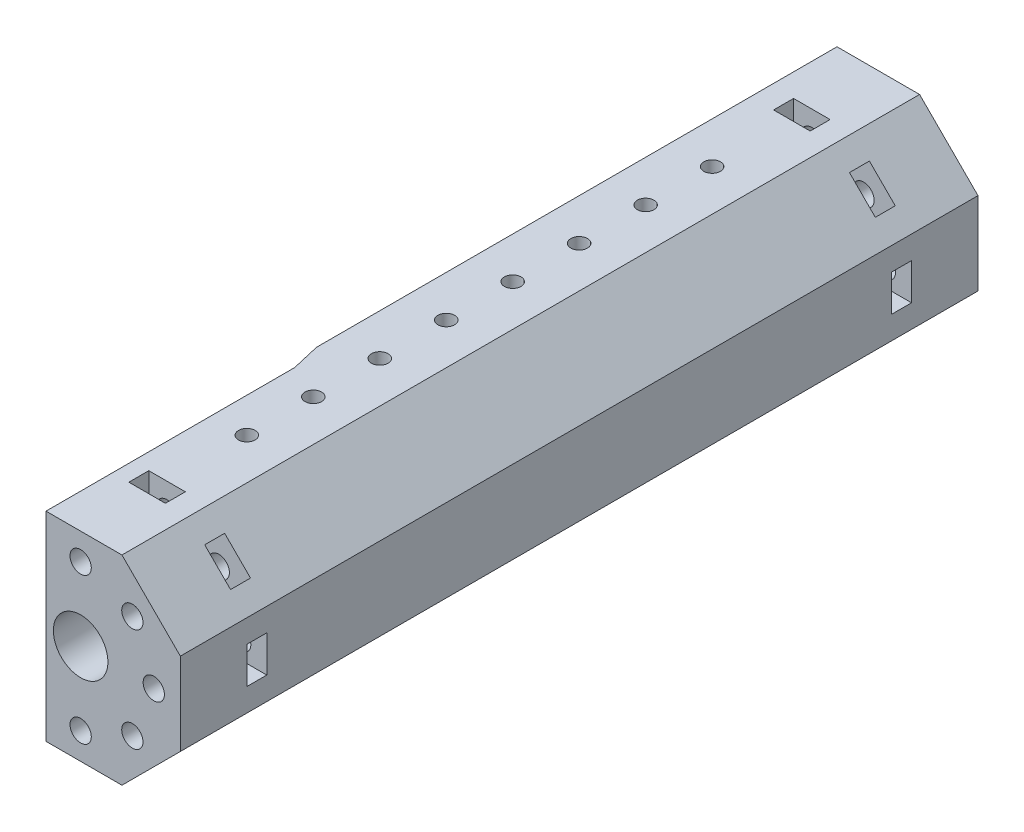
SolidWorks part; units mm, degrees
ref_plane "Alzado" through (0, 0, 0) normal (0, 0, 1) x (1, 0, 0)
ref_plane "Planta" through (0, 0, 0) normal (0, 1, 0) x (1, 0, 0)
ref_plane "Vista lateral" through (0, 0, 0) normal (1, 0, 0) x (0, 0, -1)
sketch "Croquis1" plane through (0, 0, 0) normal (0, 0, 1) x (1, 0, 0)
  line L1 (15, -6.2132) -> (15, 6.2132)
  line L2 (15, 6.2132) -> (6.2132, 15)
  line L3 (6.2132, 15) -> (-6.2132, 15)
  line L4 (-6.2132, 15) -> (-15, 6.2132)
  line L5 (-15, 6.2132) -> (-15, -6.2132)
  line L6 (-15, -6.2132) -> (-6.2132, -15)
  line L7 (-6.2132, -15) -> (6.2132, -15)
  line L8 (6.2132, -15) -> (15, -6.2132)
  circle A0 centre (0, 0) radius 15 construction
  dimension "D1" = 30
extrude "Saliente-Extruir1" add sketch "Croquis1" along normal blind 60
sketch "Croquis2" plane through (0, 0, 0) normal (0, 0, -1) x (-1, 0, 0)
  circle A0 centre (0, 11) radius 1.6
  circle A2 centre (7.7782, 7.7782) radius 1.6
  circle A3 centre (11, 0) radius 1.6
  circle A4 centre (7.7782, -7.7782) radius 1.6
  circle A5 centre (0, -11) radius 1.6
  circle A6 centre (-7.7782, -7.7782) radius 1.6
  circle A7 centre (-11, 0) radius 1.6
  circle A8 centre (-7.7782, 7.7782) radius 1.6
  point P22 (0, 0)
  dimension "D1" = 3.2
  dimension "D2" = 11
  dimension "D4" = 8
extrude "Cortar-Extruir1" cut sketch "Croquis2" against normal blind 20
sketch "Croquis3" plane through (0, 0, 0) normal (0, 0, -1) x (-1, 0, 0)
  line L0 (-2.75, 12.5877) -> (-2.75, 18.4632)
  line L1 (2.75, 12.5877) -> (0, 14.1754) construction
  line L2 (0, 14.1754) -> (-2.75, 12.5877) construction
  line L3 (-2.75, 12.5877) -> (-2.75, 9.4123)
  line L4 (-2.75, 9.4123) -> (0, 7.8246)
  line L5 (0, 7.8246) -> (2.75, 9.4123)
  line L6 (2.75, 9.4123) -> (2.75, 12.5877)
  line L7 (-15, 6.2132) -> (-6.2132, 15) construction
  line L8 (-2.75, 18.4632) -> (2.75, 23.9632)
  line L9 (2.75, 23.9632) -> (2.75, 12.5877)
  line L10 (6.9563, 10.8454) -> (11.1109, 15)
  line L11 (6.9563, 10.8454) -> (4.7109, 8.6)
  line L12 (4.7109, 8.6) -> (5.5328, 5.5328)
  line L13 (5.5328, 5.5328) -> (8.6, 4.7109)
  line L14 (8.6, 4.7109) -> (10.8454, 6.9563)
  line L15 (11.1109, 15) -> (18.8891, 15)
  line L16 (18.8891, 15) -> (10.8454, 6.9563)
  line L17 (10.8454, 6.9563) -> (10.0235, 10.0235) construction
  line L18 (10.0235, 10.0235) -> (6.9563, 10.8454) construction
  line L19 (12.5877, 2.75) -> (18.4632, 2.75)
  line L20 (12.5877, 2.75) -> (9.4123, 2.75)
  line L21 (9.4123, 2.75) -> (7.8246, 0)
  line L22 (7.8246, 0) -> (9.4123, -2.75)
  line L23 (9.4123, -2.75) -> (12.5877, -2.75)
  line L24 (18.4632, 2.75) -> (23.9632, -2.75)
  line L25 (23.9632, -2.75) -> (12.5877, -2.75)
  line L26 (12.5877, -2.75) -> (14.1754, 0) construction
  line L27 (14.1754, 0) -> (12.5877, 2.75) construction
  line L28 (10.8454, -6.9563) -> (15, -11.1109)
  line L29 (10.8454, -6.9563) -> (8.6, -4.7109)
  line L30 (8.6, -4.7109) -> (5.5328, -5.5328)
  line L31 (5.5328, -5.5328) -> (4.7109, -8.6)
  line L32 (4.7109, -8.6) -> (6.9563, -10.8454)
  line L33 (15, -11.1109) -> (15, -18.8891)
  line L34 (15, -18.8891) -> (6.9563, -10.8454)
  line L35 (6.9563, -10.8454) -> (10.0235, -10.0235) construction
  line L36 (10.0235, -10.0235) -> (10.8454, -6.9563) construction
  line L37 (2.75, -12.5877) -> (2.75, -18.4632)
  line L38 (2.75, -12.5877) -> (2.75, -9.4123)
  line L39 (2.75, -9.4123) -> (0, -7.8246)
  line L40 (0, -7.8246) -> (-2.75, -9.4123)
  line L41 (-2.75, -9.4123) -> (-2.75, -12.5877)
  line L42 (2.75, -18.4632) -> (-2.75, -23.9632)
  line L43 (-2.75, -23.9632) -> (-2.75, -12.5877)
  line L44 (-2.75, -12.5877) -> (0, -14.1754) construction
  line L45 (0, -14.1754) -> (2.75, -12.5877) construction
  line L46 (-6.9563, -10.8454) -> (-11.1109, -15)
  line L47 (-6.9563, -10.8454) -> (-4.7109, -8.6)
  line L48 (-4.7109, -8.6) -> (-5.5328, -5.5328)
  line L49 (-5.5328, -5.5328) -> (-8.6, -4.7109)
  line L50 (-8.6, -4.7109) -> (-10.8454, -6.9563)
  line L51 (-11.1109, -15) -> (-18.8891, -15)
  line L52 (-18.8891, -15) -> (-10.8454, -6.9563)
  line L53 (-10.8454, -6.9563) -> (-10.0235, -10.0235) construction
  line L54 (-10.0235, -10.0235) -> (-6.9563, -10.8454) construction
  line L55 (-12.5877, -2.75) -> (-18.4632, -2.75)
  line L56 (-12.5877, -2.75) -> (-9.4123, -2.75)
  line L57 (-9.4123, -2.75) -> (-7.8246, 0)
  line L58 (-7.8246, 0) -> (-9.4123, 2.75)
  line L59 (-9.4123, 2.75) -> (-12.5877, 2.75)
  line L60 (-18.4632, -2.75) -> (-23.9632, 2.75)
  line L61 (-23.9632, 2.75) -> (-12.5877, 2.75)
  line L62 (-12.5877, 2.75) -> (-14.1754, 0) construction
  line L63 (-14.1754, 0) -> (-12.5877, -2.75) construction
  line L64 (-10.8454, 6.9563) -> (-15, 11.1109)
  line L65 (-10.8454, 6.9563) -> (-8.6, 4.7109)
  line L66 (-8.6, 4.7109) -> (-5.5328, 5.5328)
  line L67 (-5.5328, 5.5328) -> (-4.7109, 8.6)
  line L68 (-4.7109, 8.6) -> (-6.9563, 10.8454)
  line L69 (-15, 11.1109) -> (-15, 18.8891)
  line L70 (-15, 18.8891) -> (-6.9563, 10.8454)
  line L71 (-6.9563, 10.8454) -> (-10.0235, 10.0235) construction
  line L72 (-10.0235, 10.0235) -> (-10.8454, 6.9563) construction
  circle A0 centre (0, 11) radius 2.75 construction
  circle A1 centre (7.7782, 7.7782) radius 2.75 construction
  circle A2 centre (11, 0) radius 2.75 construction
  circle A3 centre (7.7782, -7.7782) radius 2.75 construction
  circle A4 centre (0, -11) radius 2.75 construction
  circle A5 centre (-7.7782, -7.7782) radius 2.75 construction
  circle A6 centre (-11, 0) radius 2.75 construction
  circle A7 centre (-7.7782, 7.7782) radius 2.75 construction
  point P86 (0, 0)
  dimension "D1" = 5.5
  dimension "D2" = 8
extrude "Cortar-Extruir2" cut sketch "Croquis3" against normal blind 3 from offset 10 offset against normal yes
sketch "Croquis8" plane through (0, -15, 0) normal (0, -1, 0) x (1, 0, 0)
  line L0 (-6.2132, 0) -> (6.2132, 0) construction
  circle A0 centre (0, 25) radius 1.25
  point P5 (0, 0)
  dimension "D1" = 2.5
  dimension "D2" = 25
mirror "Simetría1" about plane through (0, 0, 60) normal (0, 0, 1) of "Saliente-Extruir1"
sketch "Croquis4" plane through (0, 0, 0) normal (0, 0, -1) x (-1, 0, 0)
  circle A0 centre (0, 0) radius 4.1
  dimension "D1" = 8.2
extrude "Cortar-Extruir3" cut sketch "Croquis4" against normal through all
sketch "Croquis5" plane through (0, -15, 0) normal (0, -1, 0) x (1, 0, 0)
  line L0 (-6.2132, 120) -> (-6.2132, 78.2987)
  line L1 (-6.2132, 120) -> (-6.2132, 0) construction
  line L2 (-6.2132, 78.2987) -> (-15, 40.5695)
  line L3 (-15, 120) -> (-15, 0) construction
  line L4 (-15, 40.5695) -> (-15, 120)
  line L5 (-15, 120) -> (-6.2132, 120)
extrude "Cortar-Extruir4" cut sketch "Croquis5" against normal through all
sketch "Croquis6" plane through (0, 0, 120) normal (0, 0, 1) x (1, 0, 0)
  circle A0 centre (0, 11) radius 1.6
  circle A2 centre (7.7782, 7.7782) radius 1.6
  circle A3 centre (11, 0) radius 1.6
  circle A4 centre (7.7782, -7.7782) radius 1.6
  circle A5 centre (0, -11) radius 1.6
  circle A9 centre (-7.7782, 7.7782) radius 1.6 [skipped]
  circle A10 centre (-11, 0) radius 1.6 [skipped]
  circle A11 centre (-7.7782, -7.7782) radius 1.6 [skipped]
  point P22 (0, 0)
  dimension "D1" = 3.2
  dimension "D2" = 11
  dimension "D4" = 8
sketch "Croquis7" plane through (0, 0, 120) normal (0, 0, 1) x (1, 0, 0)
  line L0 (-2.75, 12.5877) -> (-2.75, 18.4632)
  line L1 (2.75, 12.5877) -> (0, 14.1754) construction
  line L2 (0, 14.1754) -> (-2.75, 12.5877) construction
  line L3 (-2.75, 12.5877) -> (-2.75, 9.4123)
  line L4 (-2.75, 9.4123) -> (0, 7.8246)
  line L5 (0, 7.8246) -> (2.75, 9.4123)
  line L6 (2.75, 9.4123) -> (2.75, 12.5877)
  line L8 (-2.75, 18.4632) -> (2.75, 23.9632)
  line L9 (2.75, 23.9632) -> (2.75, 12.5877)
  line L10 (6.9563, 10.8454) -> (11.1109, 15)
  line L11 (6.9563, 10.8454) -> (4.7109, 8.6)
  line L12 (4.7109, 8.6) -> (5.5328, 5.5328)
  line L13 (5.5328, 5.5328) -> (8.6, 4.7109)
  line L14 (8.6, 4.7109) -> (10.8454, 6.9563)
  line L15 (11.1109, 15) -> (18.8891, 15)
  line L16 (18.8891, 15) -> (10.8454, 6.9563)
  line L17 (10.8454, 6.9563) -> (10.0235, 10.0235) construction
  line L18 (10.0235, 10.0235) -> (6.9563, 10.8454) construction
  line L19 (12.5877, 2.75) -> (18.4632, 2.75)
  line L20 (12.5877, 2.75) -> (9.4123, 2.75)
  line L21 (9.4123, 2.75) -> (7.8246, 0)
  line L22 (7.8246, 0) -> (9.4123, -2.75)
  line L23 (9.4123, -2.75) -> (12.5877, -2.75)
  line L24 (18.4632, 2.75) -> (23.9632, -2.75)
  line L25 (23.9632, -2.75) -> (12.5877, -2.75)
  line L26 (12.5877, -2.75) -> (14.1754, 0) construction
  line L27 (14.1754, 0) -> (12.5877, 2.75) construction
  line L28 (10.8454, -6.9563) -> (15, -11.1109)
  line L29 (10.8454, -6.9563) -> (8.6, -4.7109)
  line L30 (8.6, -4.7109) -> (5.5328, -5.5328)
  line L31 (5.5328, -5.5328) -> (4.7109, -8.6)
  line L32 (4.7109, -8.6) -> (6.9563, -10.8454)
  line L33 (15, -11.1109) -> (15, -18.8891)
  line L34 (15, -18.8891) -> (6.9563, -10.8454)
  line L35 (6.9563, -10.8454) -> (10.0235, -10.0235) construction
  line L36 (10.0235, -10.0235) -> (10.8454, -6.9563) construction
  line L37 (2.75, -12.5877) -> (2.75, -18.4632)
  line L38 (2.75, -12.5877) -> (2.75, -9.4123)
  line L39 (2.75, -9.4123) -> (0, -7.8246)
  line L40 (0, -7.8246) -> (-2.75, -9.4123)
  line L41 (-2.75, -9.4123) -> (-2.75, -12.5877)
  line L42 (2.75, -18.4632) -> (-2.75, -23.9632)
  line L43 (-2.75, -23.9632) -> (-2.75, -12.5877)
  line L44 (-2.75, -12.5877) -> (0, -14.1754) construction
  line L45 (0, -14.1754) -> (2.75, -12.5877) construction
  line L46 (-6.9563, -10.8454) -> (-11.1109, -15) construction
  line L47 (-6.9563, -10.8454) -> (-4.7109, -8.6) construction
  line L48 (-4.7109, -8.6) -> (-5.5328, -5.5328) construction
  line L49 (-5.5328, -5.5328) -> (-8.6, -4.7109) construction
  line L50 (-8.6, -4.7109) -> (-10.8454, -6.9563) construction
  line L51 (-11.1109, -15) -> (-18.8891, -15) construction
  line L52 (-18.8891, -15) -> (-10.8454, -6.9563) construction
  line L53 (-10.8454, -6.9563) -> (-10.0235, -10.0235) construction
  line L54 (-10.0235, -10.0235) -> (-6.9563, -10.8454) construction
  line L55 (-12.5877, -2.75) -> (-18.4632, -2.75) construction
  line L56 (-12.5877, -2.75) -> (-9.4123, -2.75) construction
  line L57 (-9.4123, -2.75) -> (-7.8246, 0) construction
  line L58 (-7.8246, 0) -> (-9.4123, 2.75) construction
  line L59 (-9.4123, 2.75) -> (-12.5877, 2.75) construction
  line L60 (-18.4632, -2.75) -> (-23.9632, 2.75) construction
  line L61 (-23.9632, 2.75) -> (-12.5877, 2.75) construction
  line L62 (-12.5877, 2.75) -> (-14.1754, 0) construction
  line L63 (-14.1754, 0) -> (-12.5877, -2.75) construction
  line L64 (-10.8454, 6.9563) -> (-15, 11.1109) construction
  line L65 (-10.8454, 6.9563) -> (-8.6, 4.7109) construction
  line L66 (-8.6, 4.7109) -> (-5.5328, 5.5328) construction
  line L67 (-5.5328, 5.5328) -> (-4.7109, 8.6) construction
  line L68 (-4.7109, 8.6) -> (-6.9563, 10.8454) construction
  line L69 (-15, 11.1109) -> (-15, 18.8891) construction
  line L70 (-15, 18.8891) -> (-6.9563, 10.8454) construction
  line L71 (-6.9563, 10.8454) -> (-10.0235, 10.0235) construction
  line L72 (-10.0235, 10.0235) -> (-10.8454, 6.9563) construction
  circle A0 centre (0, 11) radius 2.75 construction
  circle A1 centre (7.7782, 7.7782) radius 2.75 construction
  circle A2 centre (11, 0) radius 2.75 construction
  circle A3 centre (7.7782, -7.7782) radius 2.75 construction
  circle A4 centre (0, -11) radius 2.75 construction
  circle A5 centre (-7.7782, -7.7782) radius 2.75 construction
  circle A6 centre (-11, 0) radius 2.75 construction
  circle A7 centre (-7.7782, 7.7782) radius 2.75 construction
  point P86 (0, 0)
  dimension "D1" = 5.5
  dimension "D2" = 8
extrude "Cortar-Extruir5" cut sketch "Croquis6" against normal blind 20
extrude "Cortar-Extruir6" cut sketch "Croquis7" against normal blind 3 from offset 10 offset against normal yes
extrude "Cortar-Extruir8" cut sketch "Croquis8" against normal through all
pattern_linear "MatrizL1" count 8 spacing 10 along (0, 0, 1) of "Cortar-Extruir8"
chamfer "Chaflán1" distance 1 angle 45 3 edges at (-6.2132, 15, 99.1494) (-6.2132, -15, 99.1494) (-6.2132, 0, 120)
